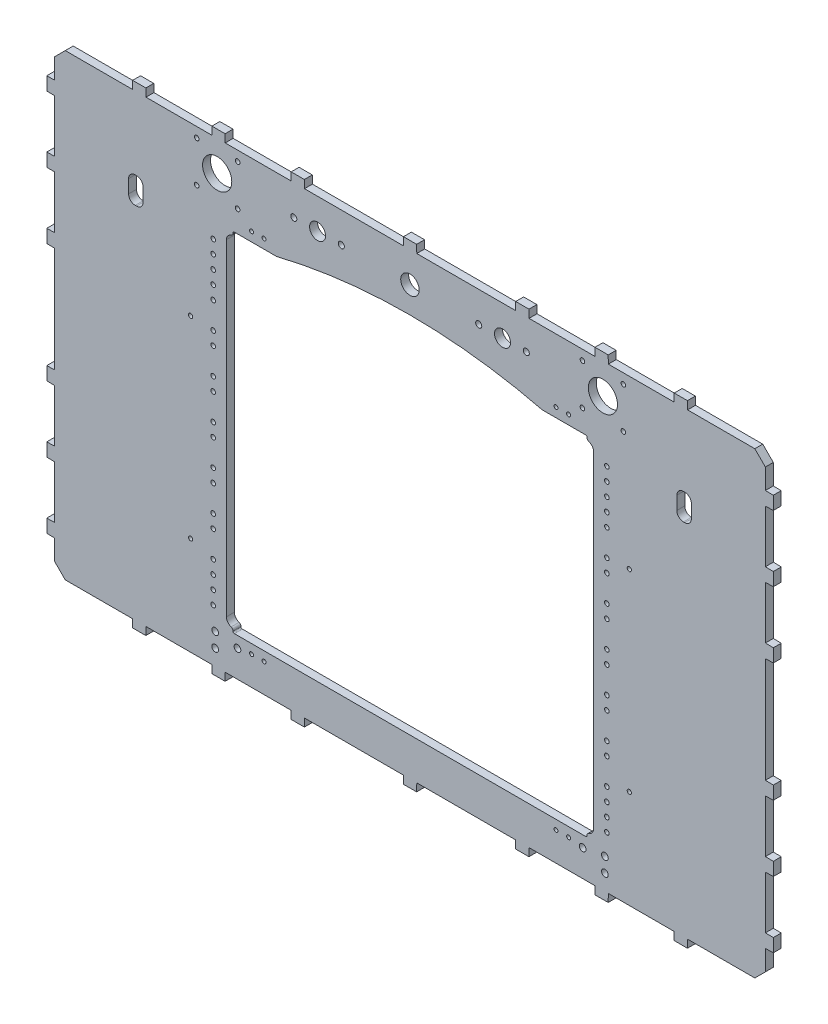
SolidWorks part; units mm, degrees
material "Клен"
ref_plane "Front" through (0, 0, 0) normal (0, 0, 1) x (1, 0, 0)
ref_plane "Top" through (0, 0, 0) normal (0, 1, 0) x (1, 0, 0)
ref_plane "Right" through (0, 0, 0) normal (1, 0, 0) x (0, 0, -1)
sketch "Эскиз1" plane through (0, 0, 0) normal (0, 0, 1) x (1, 0, 0)
  line L0 (2003.9536, 671.6913) -> (1788.4175, 671.6913) construction
  line L1 (1693.5265, 694.1913) -> (1693.5265, 791.8131) construction
  line L2 (1962.5805, 811.45) -> (1962.5805, 379.7662) construction
  line L3 (1554.5805, 451.4706) -> (1554.5805, 698.6913)
  line L4 (1559.5805, 705.6913) -> (1559.5805, 705.3995)
  line L5 (1560.5805, 706.6913) -> (1592.5638, 706.6913)
  line L6 (1862.5805, 811.45) -> (1862.5805, 379.7662) construction
  line L7 (1486.5125, 686.6913) -> (1485.5125, 686.6913)
  line L8 (1900.5405, 706.6913) -> (1901.5405, 706.6913)
  line L9 (1895.5405, 701.6913) -> (1895.5405, 691.6913)
  line L10 (1900.5405, 686.6913) -> (1901.5405, 686.6913)
  line L11 (1906.5405, 701.6913) -> (1906.5405, 691.6913)
  line L12 (1559.5805, 444.7624) -> (1559.5805, 444.4706)
  line L13 (1560.5805, 443.4706) -> (1826.5797, 443.4706)
  line L14 (1827.5797, 444.7624) -> (1827.5797, 444.4706)
  line L15 (1832.5805, 698.6913) -> (1832.5797, 451.4706)
  line L16 (1827.5805, 705.6913) -> (1827.5805, 705.3995)
  line L17 (1826.5805, 706.6913) -> (1793.6805, 706.6913)
  line L18 (1843.6805, 414.6913) -> (1893.4805, 414.6913)
  line L20 (1524.5805, 795.1278) -> (1524.5805, 392.3884) construction
  line L21 (1424.5805, 392.3884) -> (1424.5805, 795.1278) construction
  line L22 (1424.5805, 738.2913) -> (1418.5805, 738.1913)
  line L23 (1418.5805, 498.1913) -> (1418.5805, 488.1913)
  line L24 (1424.5805, 638.2913) -> (1418.5805, 638.1913)
  line L25 (1424.5805, 728.0913) -> (1424.5805, 688.2913)
  line L26 (1418.5805, 548.1913) -> (1418.5805, 538.1913)
  line L27 (1424.5805, 753.6913) -> (1424.5805, 738.2913)
  line L28 (1418.5805, 538.1913) -> (1424.5805, 538.0913)
  line L29 (1418.5805, 438.1913) -> (1424.5805, 438.0913)
  line L30 (1418.5805, 448.1913) -> (1418.5805, 438.1913)
  line L31 (1418.5805, 738.1913) -> (1418.5805, 728.1913)
  line L32 (1418.5805, 638.1913) -> (1418.5805, 628.1913)
  line L33 (1418.5805, 628.1913) -> (1424.5805, 628.0913)
  line L34 (1424.5805, 448.2913) -> (1418.5805, 448.1913)
  line L35 (1424.5805, 498.2913) -> (1418.5805, 498.1913)
  line L36 (1424.5805, 688.2913) -> (1418.5805, 688.1913)
  line L37 (1418.5805, 678.1913) -> (1424.5805, 678.0913)
  line L38 (1418.5805, 488.1913) -> (1424.5805, 488.0913)
  line L39 (1424.5805, 422.6913) -> (1432.5805, 414.6913)
  line L40 (1418.5805, 688.1913) -> (1418.5805, 678.1913)
  line L41 (1424.5805, 628.0913) -> (1424.5805, 548.2913)
  line L42 (1424.5805, 538.0913) -> (1424.5805, 498.2913)
  line L43 (1424.5805, 488.0913) -> (1424.5805, 448.2913)
  line L44 (1424.5805, 438.0913) -> (1424.5805, 422.6913)
  line L45 (1424.5805, 678.0913) -> (1424.5805, 638.2913)
  line L46 (1424.5805, 548.2913) -> (1418.5805, 548.1913)
  line L47 (1432.5805, 761.6913) -> (1424.5805, 753.6913)
  line L48 (1418.5805, 728.1913) -> (1424.5805, 728.0913)
  line L49 (1432.5805, 761.6913) -> (1483.4805, 761.6913)
  line L50 (1432.5805, 414.6913) -> (1483.4805, 414.6913)
  line L51 (1968.5805, 538.1913) -> (1968.5805, 548.1913)
  line L52 (1962.5805, 498.2913) -> (1962.5805, 538.0913)
  line L53 (1968.5805, 728.1913) -> (1968.5805, 738.1913)
  line L54 (1962.5805, 438.0913) -> (1968.5805, 438.1913)
  line L55 (1962.5805, 628.0913) -> (1968.5805, 628.1913)
  line L56 (1968.5805, 548.1913) -> (1962.5805, 548.2913)
  line L57 (1968.5805, 678.1913) -> (1968.5805, 688.1913)
  line L58 (1962.5805, 688.2913) -> (1962.5805, 728.0913)
  line L59 (1962.5805, 448.2913) -> (1962.5805, 488.0913)
  line L60 (1968.5805, 488.1913) -> (1968.5805, 498.1913)
  line L61 (1962.5805, 548.2913) -> (1962.5805, 628.0913)
  line L62 (1962.5805, 738.2913) -> (1962.5805, 753.6913)
  line L63 (1968.5805, 438.1913) -> (1968.5805, 448.1913)
  line L64 (1962.5805, 638.2913) -> (1962.5805, 678.0913)
  line L65 (1962.5805, 422.6913) -> (1962.5805, 438.0913)
  line L66 (1968.5805, 628.1913) -> (1968.5805, 638.1913)
  line L67 (1968.5805, 738.1913) -> (1962.5805, 738.2913)
  line L68 (1962.5805, 488.0913) -> (1968.5805, 488.1913)
  line L69 (1968.5805, 688.1913) -> (1962.5805, 688.2913)
  line L70 (1968.5805, 498.1913) -> (1962.5805, 498.2913)
  line L71 (1962.5805, 728.0913) -> (1968.5805, 728.1913)
  line L72 (1962.5805, 753.6913) -> (1954.5805, 761.6913)
  line L73 (1954.5805, 414.6913) -> (1962.5805, 422.6913)
  line L74 (1968.5805, 448.1913) -> (1962.5805, 448.2913)
  line L75 (1962.5805, 538.0913) -> (1968.5805, 538.1913)
  line L76 (1968.5805, 638.1913) -> (1962.5805, 638.2913)
  line L77 (1962.5805, 678.0913) -> (1968.5805, 678.1913)
  line L78 (1854.5805, 761.6913) -> (1893.4805, 761.6913)
  line L80 (1903.5805, 767.6913) -> (1893.5805, 767.6913)
  line L81 (1903.6805, 761.6913) -> (1903.5805, 767.6913)
  line L82 (1893.5805, 767.6913) -> (1893.4805, 761.6913)
  line L83 (1483.5805, 767.6913) -> (1483.4805, 761.6913)
  line L84 (1493.5805, 767.6913) -> (1483.5805, 767.6913)
  line L85 (1493.6805, 761.6913) -> (1493.5805, 767.6913)
  line L86 (1493.6805, 761.6913) -> (1532.5805, 761.6913)
  line L87 (1903.6805, 761.6913) -> (1954.5805, 761.6913)
  line L88 (1893.4805, 414.6913) -> (1893.5805, 408.6913)
  line L89 (1903.5805, 408.6913) -> (1903.6805, 414.6913)
  line L90 (1893.5805, 408.6913) -> (1903.5805, 408.6913)
  line L91 (1493.5805, 408.6913) -> (1493.6805, 414.6913)
  line L92 (1483.4805, 414.6913) -> (1483.5805, 408.6913)
  line L93 (1483.5805, 408.6913) -> (1493.5805, 408.6913)
  line L94 (1493.6805, 414.6913) -> (1532.5805, 414.6913)
  line L95 (1903.6805, 414.6913) -> (1954.5805, 414.6913)
  line L96 (1892.5805, 811.45) -> (1892.5805, 392.5098) construction
  line L97 (1494.5805, 795.1278) -> (1494.5805, 392.3884) construction
  line L98 (2003.9536, 706.6913) -> (1401.3159, 706.6913) construction
  line L99 (1480.5125, 701.6913) -> (1480.5125, 691.6913)
  line L104 (1486.5125, 706.6913) -> (1485.5125, 706.6913)
  line L105 (1491.5125, 701.6913) -> (1491.5125, 691.6913)
  line L106 (1859.5805, 811.45) -> (1859.5805, 401.8133) construction
  line L107 (1847.3817, 489.2413) -> (1981.6541, 489.2413) construction
  line L108 (1847.3817, 635.2413) -> (1981.6541, 635.2413) construction
  line L192 (1613.5805, 408.6913) -> (1613.6805, 414.6913)
  line L193 (1613.6805, 414.6913) -> (1688.4805, 414.6913)
  line L194 (1688.4805, 414.6913) -> (1688.5805, 408.6913)
  line L195 (1688.5805, 408.6913) -> (1698.5805, 408.6913)
  line L196 (1698.5805, 408.6913) -> (1698.6805, 414.6913)
  line L197 (1698.6805, 414.6913) -> (1773.4805, 414.6913)
  line L198 (1773.4805, 414.6913) -> (1773.5805, 408.6913)
  line L199 (1773.5805, 408.6913) -> (1783.5805, 408.6913)
  line L200 (1783.5805, 408.6913) -> (1783.6805, 414.6913)
  line L201 (1783.6805, 414.6913) -> (1833.4805, 414.6913)
  line L202 (1833.4805, 414.6913) -> (1833.5805, 408.6913)
  line L203 (1833.5805, 408.6913) -> (1843.5805, 408.6913)
  line L204 (1843.5805, 408.6913) -> (1843.6805, 414.6913)
  line L233 (1854.5805, 761.6913) -> (1843.6805, 761.6913)
  line L234 (1843.6805, 761.6913) -> (1843.5805, 767.6913)
  line L235 (1843.5805, 767.6913) -> (1833.5805, 767.6913)
  line L236 (1833.5805, 767.6913) -> (1833.4805, 761.6913)
  line L237 (1833.4805, 761.6913) -> (1783.6805, 761.6913)
  line L238 (1783.6805, 761.6913) -> (1783.5805, 767.6913)
  line L239 (1783.5805, 767.6913) -> (1773.5805, 767.6913)
  line L240 (1773.5805, 767.6913) -> (1773.4805, 761.6913)
  line L241 (1773.4805, 761.6913) -> (1698.6805, 761.6913)
  line L242 (1698.6805, 761.6913) -> (1698.5805, 767.6913)
  line L243 (1698.5805, 767.6913) -> (1688.5805, 767.6913)
  line L244 (1688.5805, 767.6913) -> (1688.4805, 761.6913)
  line L245 (1688.4805, 761.6913) -> (1613.6805, 761.6913)
  line L246 (1613.6805, 761.6913) -> (1613.5805, 767.6913)
  line L247 (1613.5805, 767.6913) -> (1603.5805, 767.6913)
  line L248 (1603.5805, 767.6913) -> (1603.4805, 761.6913)
  line L249 (1603.4805, 761.6913) -> (1553.6805, 761.6913)
  line L250 (1553.6805, 761.6913) -> (1553.5805, 767.6913)
  line L251 (1553.5805, 767.6913) -> (1543.5805, 767.6913)
  line L252 (1543.5805, 767.6913) -> (1543.4805, 761.6913)
  line L253 (1543.4805, 761.6913) -> (1532.5805, 761.6913)
  line L281 (1532.5805, 414.6913) -> (1543.4805, 414.6913)
  line L282 (1543.4805, 414.6913) -> (1543.5805, 408.6913)
  line L283 (1543.5805, 408.6913) -> (1553.5805, 408.6913)
  line L284 (1553.5805, 408.6913) -> (1553.6805, 414.6913)
  line L285 (1553.6805, 414.6913) -> (1603.4805, 414.6913)
  line L286 (1603.4805, 414.6913) -> (1603.5805, 408.6913)
  line L287 (1603.5805, 408.6913) -> (1613.5805, 408.6913)
  arc A0 (1901.5405, 686.6913) -> (1906.5405, 691.6913) centre (1901.5405, 691.6913) ccw
  arc A1 (1895.5405, 691.6913) -> (1900.5405, 686.6913) centre (1900.5405, 691.6913) ccw
  arc A2 (1901.5405, 706.6913) -> (1906.5405, 701.6913) centre (1901.5405, 701.6913) cw
  arc A3 (1900.5405, 706.6913) -> (1895.5405, 701.6913) centre (1900.5405, 701.6913) ccw
  arc A4 (1485.5125, 686.6913) -> (1480.5125, 691.6913) centre (1485.5125, 691.6913) cw
  arc A5 (1485.5125, 706.6913) -> (1480.5125, 701.6913) centre (1485.5125, 701.6913) ccw
  arc A6 (1491.5125, 691.6913) -> (1486.5125, 686.6913) centre (1486.5125, 691.6913) cw
  arc A7 (1486.5125, 706.6913) -> (1491.5125, 701.6913) centre (1486.5125, 701.6913) cw
  circle A8 centre (1859.5805, 489.2413) radius 1.6
  circle A9 centre (1859.5805, 635.2413) radius 1.6
  circle A10 centre (1527.4726, 489.2413) radius 1.6
  circle A11 centre (1527.4726, 635.2413) radius 1.6
  circle A69 centre (1804.0805, 436.4706) radius 1.5
  circle A70 centre (1813.5805, 436.4706) radius 1.5
  circle A71 centre (1824.2277, 434.9809) radius 2.55
  circle A72 centre (1841.0805, 426.6913) radius 2.55
  circle A73 centre (1841.0805, 437.6913) radius 2.55
  circle A74 centre (1842.5805, 454.1913) radius 1.75
  circle A75 centre (1842.5805, 464.1913) radius 1.75
  circle A76 centre (1842.5805, 474.1913) radius 1.75
  circle A77 centre (1842.5805, 484.1913) radius 1.75
  circle A78 centre (1842.5805, 504.1913) radius 1.75
  circle A79 centre (1842.5805, 514.1913) radius 1.75
  circle A80 centre (1842.5805, 534.1913) radius 1.75
  circle A81 centre (1842.5805, 544.1913) radius 1.75
  circle A82 centre (1842.5805, 564.1913) radius 1.75
  circle A83 centre (1842.5805, 574.1913) radius 1.75
  circle A84 centre (1842.5805, 594.1913) radius 1.75
  circle A85 centre (1842.5805, 604.1913) radius 1.75
  circle A86 centre (1842.5805, 624.1913) radius 1.75
  circle A87 centre (1842.5805, 634.1913) radius 1.75
  circle A88 centre (1842.5805, 654.1913) radius 1.75
  circle A89 centre (1842.5805, 664.1913) radius 1.75
  circle A90 centre (1842.5805, 674.1913) radius 1.75
  circle A91 centre (1842.5805, 684.1913) radius 1.75
  circle A92 centre (1842.5805, 694.1913) radius 1.75
  circle A93 centre (1583.0805, 436.4706) radius 1.5
  circle A94 centre (1573.5805, 436.4706) radius 1.5
  circle A95 centre (1562.9305, 434.9809) radius 2.55
  circle A96 centre (1546.0805, 426.6913) radius 2.55
  circle A97 centre (1546.0805, 437.6913) radius 2.55
  circle A98 centre (1544.5805, 454.1913) radius 1.75
  circle A99 centre (1544.5805, 464.1913) radius 1.75
  circle A100 centre (1544.5805, 474.1913) radius 1.75
  circle A101 centre (1544.5805, 484.1913) radius 1.75
  circle A102 centre (1544.5805, 504.1913) radius 1.75
  circle A103 centre (1544.5805, 514.1913) radius 1.75
  circle A104 centre (1544.5805, 534.1913) radius 1.75
  circle A105 centre (1544.5805, 544.1913) radius 1.75
  circle A106 centre (1544.5805, 564.1913) radius 1.75
  circle A107 centre (1544.5805, 574.1913) radius 1.75
  circle A108 centre (1544.5805, 594.1913) radius 1.75
  circle A109 centre (1544.5805, 604.1913) radius 1.75
  circle A110 centre (1544.5805, 624.1913) radius 1.75
  circle A111 centre (1544.5805, 634.1913) radius 1.75
  circle A112 centre (1544.5805, 654.1913) radius 1.75
  circle A113 centre (1544.5805, 664.1913) radius 1.75
  circle A114 centre (1544.5805, 674.1913) radius 1.75
  circle A115 centre (1544.5805, 684.1913) radius 1.75
  circle A116 centre (1544.5805, 694.1913) radius 1.75
  circle A117 centre (1804.0805, 713.6913) radius 1.5
  circle A118 centre (1813.5805, 713.6913) radius 1.5
  circle A119 centre (1824.0805, 723.1913) radius 1.75
  circle A120 centre (1855.0805, 723.1913) radius 1.75
  circle A121 centre (1839.5805, 738.6913) radius 11.05
  circle A122 centre (1855.0805, 754.1913) radius 1.75
  circle A123 centre (1824.0805, 754.1913) radius 1.75
  circle A124 centre (1781.5805, 738.6913) radius 2.3
  circle A125 centre (1763.5805, 738.6913) radius 6.05
  circle A126 centre (1745.5805, 738.6913) radius 2.3
  circle A127 centre (1693.5265, 738.6913) radius 7
  circle A128 centre (1641.5805, 738.6913) radius 2.3
  circle A129 centre (1623.5805, 738.6913) radius 6.05
  circle A130 centre (1605.5805, 738.6913) radius 2.3
  circle A131 centre (1583.0805, 713.6913) radius 1.5
  circle A132 centre (1573.5805, 713.6913) radius 1.5
  circle A133 centre (1563.0805, 723.1913) radius 1.75
  circle A134 centre (1563.0805, 754.1913) radius 1.75
  circle A135 centre (1547.5805, 738.6913) radius 11.05
  circle A136 centre (1532.0805, 723.1913) radius 1.75
  circle A137 centre (1532.0805, 754.1913) radius 1.75
  arc A142 (1793.6805, 706.6913) -> (1592.5638, 706.6913) centre (1693.1221, 296.6279) ccw
  arc A143 (1558.1519, 703.4829) -> (1554.5805, 698.6913) centre (1559.5805, 698.6913) ccw
  arc A144 (1558.1519, 703.4829) -> (1559.5805, 705.3995) centre (1557.5805, 705.3995) ccw
  arc A145 (1560.5805, 706.6913) -> (1559.5805, 705.6913) centre (1560.5805, 705.6913) ccw
  arc A155 (1559.5805, 444.4706) -> (1560.5805, 443.4706) centre (1560.5805, 444.4706) ccw
  arc A156 (1559.5805, 444.7624) -> (1558.1519, 446.6791) centre (1557.5805, 444.7624) ccw
  arc A157 (1554.5805, 451.4706) -> (1558.1519, 446.6791) centre (1559.5805, 451.4706) ccw
  arc A158 (1826.5797, 443.4706) -> (1827.5797, 444.4706) centre (1826.5797, 444.4706) ccw
  arc A159 (1829.0083, 446.6791) -> (1827.5797, 444.7624) centre (1829.5797, 444.7624) ccw
  arc A160 (1829.0083, 446.6791) -> (1832.5797, 451.4706) centre (1827.5797, 451.4706) ccw
  arc A161 (1832.5805, 698.6913) -> (1829.009, 703.4829) centre (1827.5805, 698.6913) ccw
  arc A162 (1827.5805, 705.3995) -> (1829.009, 703.4829) centre (1829.5805, 705.3995) ccw
  arc A163 (1827.5805, 705.6913) -> (1826.5805, 706.6913) centre (1826.5805, 705.6913) ccw
  point P48 (1892.5805, 696.6913)
  point P49 (1892.5805, 696.6913)
  dimension "D7" = 5
  dimension "D12" = 3.2
  dimension "D13" = 3.2
  dimension "D2" = 30
  dimension "D3" = 100
  dimension "D1" = 100
  dimension "D4" = 30
  dimension "D8" = 35
  dimension "D9" = 3
  dimension "D10" = 74.55
  dimension "D11" = 146
extrude "Бобышка-Вытянуть1" add sketch "Эскиз1" along normal blind 6
